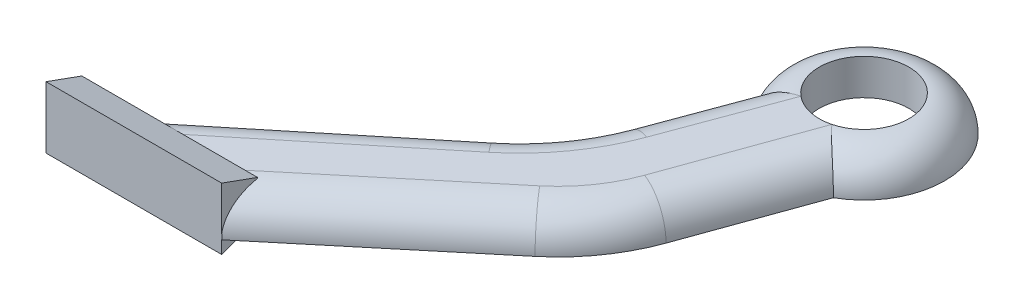
SolidWorks part; units mm, degrees
ref_plane "Front" through (0, 0, 0) normal (0, 0, 1) x (1, 0, 0)
ref_plane "Top" through (0, 0, 0) normal (0, 1, 0) x (1, 0, 0)
ref_plane "Right" through (0, 0, 0) normal (1, 0, 0) x (0, 0, -1)
sketch "Sketch1" plane through (0, 0, 0) normal (0, 1, 0) x (1, 0, 0)
  line L0 (4.7344, 4.3375) -> (-11.1234, -8.6004)
  line L1 (-11.1234, -8.6004) -> (-1.3192, -8.6004)
  line L2 (-1.3192, -8.6004) -> (10.2971, 1.0617)
  line L3 (10.2971, 1.0617) -> (13.6935, 10.4802)
  line L6 (-1.3192, -8.6004) -> (-1.3192, 14.3996) construction
  line L7 (-1.3192, 14.3996) -> (6.9826, 14.3996) construction
  line L9 (7.6119, 12.1045) -> (4.7344, 4.3375)
  circle A0 centre (11.4826, 14.3996) radius 2.5
  arc A1 (13.6935, 10.4802) -> (7.6119, 12.1045) centre (11.4826, 14.3996) ccw
  circle A2 centre (11.4826, 14.3996) radius 4.5 construction
  dimension "D1" = 2
extrude "Boss-Extrude1" add sketch "Sketch1" along normal blind 2
fillet "Fillet1" radius 10 1 edges at (10.2971, 1, -1.0617)
fillet "Fillet2" radius 10 1 edges at (4.7344, 1, -4.3375)
fillet "Fillet5" radius 2 6 edges at (6.6461, 2, -9.4976) (4.4383, 2, -4.5492) (12.4564, 2, -7.0496) (9.9999, 2, -1.2701) (-4.2493, 2, 2.992) (3.4439, 2, 4.6385)
fillet "Fillet6" radius 2 1 edges at (12.7443, 2, -18.7191)
sketch "Sketch5" plane through (0, 0, 0) normal (1, 0, 0) x (0, 0, -1)
  line L0 (-8.6004, -0.725) -> (-8.6004, 2.725)
  line L5 (-6.6004, 0) -> (-8.6004, -0.725)
  line L6 (-8.6004, 1) -> (-6.6004, 1) construction
  line L7 (-6.6004, 0) -> (-6.6004, 2)
  line L8 (-6.6004, 2) -> (-8.6004, 2.725)
  line L14 (-8.6004, 2) -> (-8.6004, 0) construction
  point P9 (-8.6004, 1)
  point P12 (-6.6004, 1)
ref_plane "Plane1" through (-6.65, 0, 0) normal (1, 0, 0) x (0, 0, -1)
sketch "Sketch6" plane through (-6.65, 0, 0) normal (1, 0, 0) x (0, 0, -1)
  line L0 (-8.6004, 2.725) -> (-6.6004, 2)
  line L1 (-6.6004, 2) -> (-6.6004, 0)
  line L2 (-6.6004, 0) -> (-8.6004, -0.725)
  line L3 (-8.6004, -0.725) -> (-8.6004, 2.725)
extrude "Boss-Extrude2" add sketch "Sketch6" along normal blind 5.3 and the other way blind 4.5
